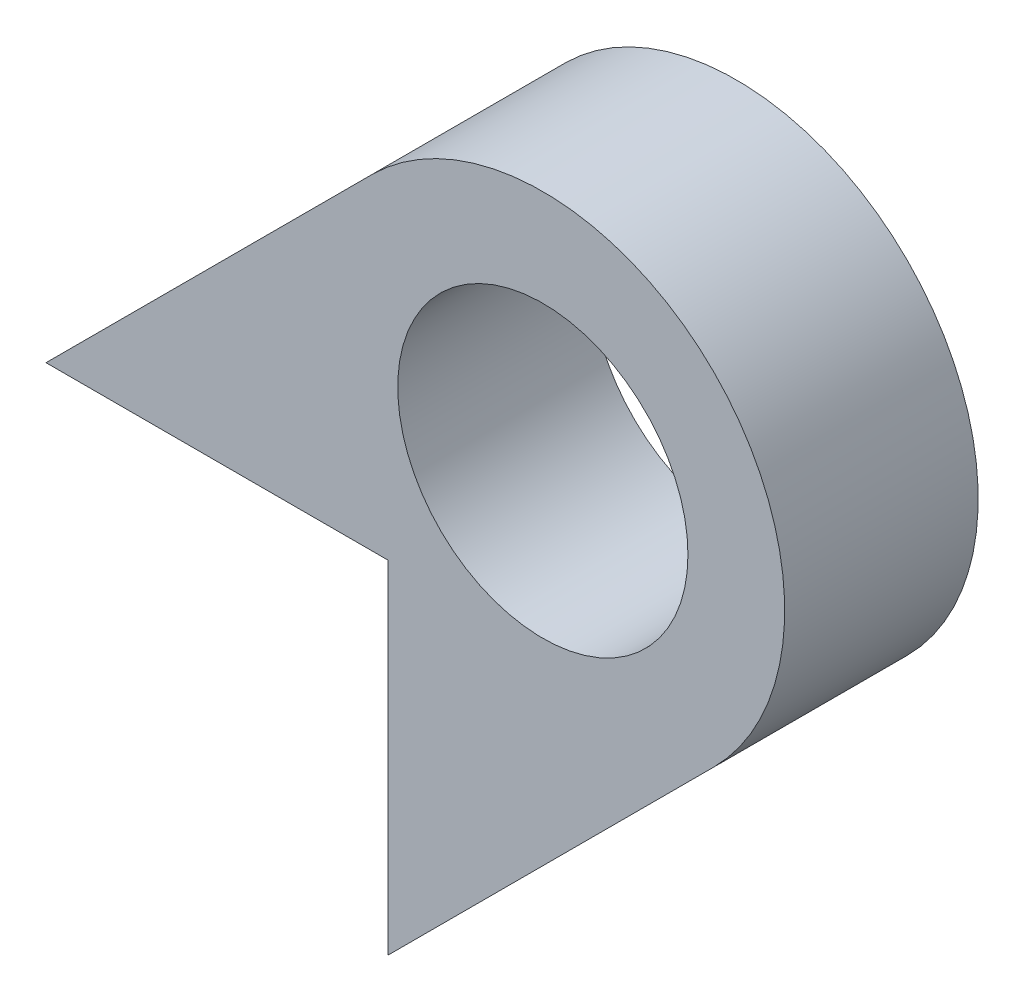
SolidWorks part; units mm, degrees
ref_plane "Front Plane" through (0, 0, 0) normal (0, 0, 1) x (1, 0, 0)
ref_plane "Top Plane" through (0, 0, 0) normal (0, 1, 0) x (1, 0, 0)
ref_plane "Right Plane" through (0, 0, 0) normal (1, 0, 0) x (0, 0, -1)
ref_axis "X" through (-88.99, 0, 0) along (1, 0, 0)
ref_axis "Y" through (0, 55, 0) along (0, -1, 0)
ref_axis "Z" through (0, 0, -88.99) along (0, 0, 1)
sketch "Sketch1" plane through (0, 0, 0) normal (0, 0, 1) x (1, 0, 0)
  line L0 (-8, -8) -> (-8, -25.6777)
  line L1 (-8, -8) -> (-25.6777, -8)
  line L2 (-25.6777, -8) -> (-8.8388, 8.8388)
  line L3 (8.8388, -8.8388) -> (-8, -25.6777)
  circle A0 centre (0, 0) radius 7.5
  arc A1 (-8.8388, 8.8388) -> (8.8388, -8.8388) centre (0, 0) cw
  point P7 (-10, -10)
  point P9 (-25.8427, -10)
  dimension "D1" = 15
  dimension "D2" = 5
  dimension "D3" = 8
  dimension "D4" = 8
extrude "Boss-Extrude1" add sketch "Sketch1" along normal blind 10
